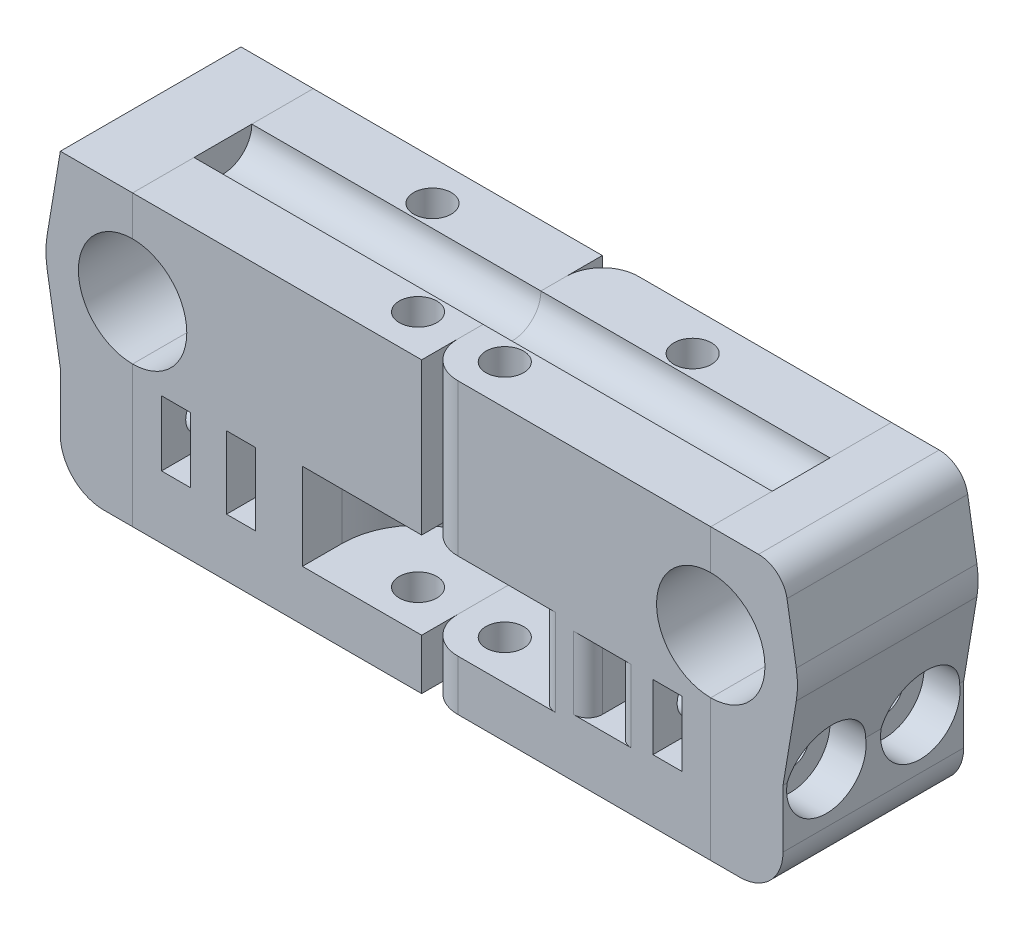
SolidWorks part; units mm, degrees
ref_plane "Front Plane" through (0, 0, 0) normal (0, 0, 1) x (1, 0, 0)
ref_plane "Top Plane" through (0, 0, 0) normal (0, 1, 0) x (1, 0, 0)
ref_plane "Right Plane" through (0, 0, 0) normal (1, 0, 0) x (0, 0, -1)
sketch "Sketch1" plane through (0, 0, 0) normal (0, 0, 1) x (1, 0, 0)
  line L0 (-15, 7) -> (-15, 0) construction
  line L1 (25, -20) -> (-25, -20)
  line L2 (25, -20) -> (25, 20)
  line L3 (25, 20) -> (-25, 20)
  line L4 (-25, -20) -> (-25, 20)
  line L5 (25, -20) -> (-25, 20) construction
  line L6 (25, 20) -> (-25, -20) construction
  line L7 (-15, 0) -> (0, 0) construction
  line L8 (-15, 7) -> (-15, -8) construction
  line L9 (-15, -8) -> (12.294, -8) construction
  line L10 (12.294, -8) -> (12.294, 8) construction
  line L11 (0, 0) -> (12.294, 0) construction
  circle A2 centre (-15, 7) radius 7.5
  point P0 (0, 0)
  dimension "D2" = 10
  dimension "D3" = 50
  dimension "D5" = 15
  dimension "D4" = 40
  dimension "D6" = 16
extrude "Boss-Extrude1" add sketch "Sketch1" along normal blind 25 contours A2 L3 L4 L1 L2
sketch "Sketch2" plane through (25, 0, 0) normal (1, 0, 0) x (0, 0, -1)
  line L0 (-25, 20) -> (0, -20) construction
  line L1 (-12.5, 20) -> (-12.5, -20) construction
  line L2 (-25, 20) -> (0, 20) construction
  circle A0 centre (-12.5, 20) radius 4
  circle A1 centre (-12.5, -20) radius 4
  point P7 (-12.5, 0)
  dimension "D2" = 8
extrude "Cut-Extrude1" cut sketch "Sketch2" against normal offset from surface (40 mm away) 10 up to face at (-25, 0, 12.5)
sketch "Sketch4" plane through (0, 20, 0) normal (0, 1, 0) x (1, 0, 0)
  line L0 (-15, -12.5) -> (13, -12.5) construction
  line L1 (19, -19.5) -> (7, -19.5) construction
  line L2 (19, -19.5) -> (19, -5.5) construction
  line L3 (19, -5.5) -> (7, -5.5) construction
  line L4 (7, -19.5) -> (7, -5.5) construction
  line L5 (19, -19.5) -> (7, -5.5) construction
  line L6 (19, -5.5) -> (7, -19.5) construction
  line L7 (-15, -8.5) -> (-15, -16.5) construction
  line L9 (-5.4237, 0) -> (-5.4237, -25)
  line L17 (-25, -25) -> (-25, 0) construction
  circle A0 centre (19, -19.5) radius 2.6
  circle A1 centre (7, -5.5) radius 2.6
  point P0 (13, -12.5)
  dimension "D3" = 5.2
  dimension "D1" = 12
  dimension "D2" = 14
  dimension "D4" = 32
extrude "Cut-Extrude2" cut sketch "Sketch4" against normal through all contours A1 | A0
sketch "Sketch7" plane through (0, 20, 0) normal (0, 1, 0) x (1, 0, 0)
  line L0 (9, 14) -> (9, -25)
  line L2 (21, -39) -> (21, 0)
  point P6 (9, -5.5)
  point P12 (21, -19.5)
sketch "Sketch16" plane through (0, 0, 0) normal (0, 0, -1) x (-1, 0, 0)
  line L1 (25, -20) -> (25, 20) construction
  line L2 (25, 20) -> (26.8369, 8.9716)
  line L3 (25, -6) -> (26.8369, 5.0284)
  line L4 (25, 20) -> (25, -6)
  circle A0 centre (15, 7) radius 12
  point P5 (27, 7)
  line M11 (25, -20) -> (25, 20)
  dimension "D1" = 2
extrude "Boss-Extrude2" add sketch "Sketch16" against normal up to surface (25 mm away) contours A0 L3 M11 | A0 L4 | A0 L2 M11
sketch "Sketch6" plane through (0, 0, 25) normal (0, 0, 1) x (1, 0, 0)
  line L0 (9.6, 20) -> (4.4, 20) construction
  line L1 (-2, -2) -> (2, -2)
  line L2 (-2, -2) -> (-2, -12)
  line L3 (-2, -12) -> (2, -12)
  line L4 (2, -2) -> (2, -12)
  line L5 (-2, -2) -> (2, -12) construction
  line L6 (-2, -12) -> (2, -2) construction
  point P0 (0, -7)
  point P5 (0, 0)
  point P6 (9, 20)
  dimension "D1" = 2
  dimension "D2" = 4
  dimension "D3" = 10
  dimension "D4" = 7
extrude "Cut-Extrude3" cut sketch "Sketch6" against normal through all
sketch "Sketch8" plane through (0, 20, 0) normal (0, 1, 0) x (1, 0, 0)
  line L0 (19, -9) -> (29.5, -9)
  line L1 (29.5, -9) -> (29.5, -30)
  line L2 (29.5, -30) -> (19, -30)
  line L3 (8.5, -19.5) -> (8.5, -30)
  line L4 (8.5, -30) -> (19, -30)
  arc A0 (19, -9) -> (8.5, -19.5) centre (19, -19.5) ccw
  dimension "D1" = 21
extrude "Cut-Extrude4" cut sketch "Sketch8" against normal blind 12 from offset 21 offset against normal yes
sketch "Sketch11" plane through (0, 20, 0) normal (0, 1, 0) x (1, 0, 0)
  line L1 (16, -5) -> (16, -10)
  line L2 (7, -16) -> (26.2266, -16)
  line L4 (16, -10) -> (26.2266, -10)
  line L5 (26.2266, -16) -> (26.2266, -10)
  line L7 (-3.5, -5.5) -> (-3.5, 3.5)
  line L8 (-3.5, 3.5) -> (16, 3.5)
  line L9 (16, -5) -> (16, 3.5)
  arc A0 (-3.5, -5.5) -> (7, -16) centre (7, -5.5) ccw
  dimension "D1" = 21
  dimension "D2" = 6
extrude "Cut-Extrude5" cut sketch "Sketch11" against normal blind 12 from offset 8 offset against normal yes
sketch "Sketch12" plane through (-25, 0, 0) normal (-1, 0, 0) x (0, 0, 1)
  line L0 (0, -20) -> (0, -6) construction
  line L1 (25, -20) -> (25, -6) construction
  line L2 (6, -6.8649) -> (19, -6.8649)
  circle A0 centre (19, -6.8649) radius 2.65
  circle A1 centre (6, -6.8649) radius 2.65
  dimension "D3" = 5.3
  dimension "D1" = 6
  dimension "D2" = 6
extrude "Cut-Extrude6" cut sketch "Sketch12" against normal blind 22
sketch "Sketch13" plane through (-25, 0, 0) normal (-1, 0, 0) x (0, 0, 1)
  line L2 (3.6139, -11.3715) -> (8.6019, -11.3715)
  line L3 (8.6019, -11.3715) -> (11.2038, -6.8649)
  line L4 (11.2038, -6.8649) -> (8.6019, -2.3583)
  line L5 (8.6019, -2.3583) -> (6, -2.3583)
  line L8 (21.5979, -2.3031) -> (16.2977, -2.4268)
  line L9 (16.2977, -2.4268) -> (13.8053, -6.9861)
  line L10 (13.8053, -6.9861) -> (16.5076, -11.4243)
  line L11 (16.5076, -11.4243) -> (21.1364, -11.3163)
  line L13 (6, -2.3583) -> (-2.7714, -2.3583)
  line L15 (3.6139, -11.3715) -> (-2.7714, -11.3715)
  line L16 (-2.7714, -2.3583) -> (-2.7714, -11.3715)
  line L17 (21.5979, -2.3031) -> (27.8928, -2.3031)
  line L19 (21.1364, -11.3163) -> (27.8928, -11.3163)
  line L20 (27.8928, -2.3031) -> (27.8928, -11.3163)
  line L21 (23.6085, -5.7809) -> (22.3774, -3.7591) [skipped]
  line L22 (22.243, -10.314) -> (23.3785, -8.237) [skipped]
  line L23 (2.0972, -4.6116) -> (0.9136, -6.6616) [skipped]
  line L24 (2.0972, -9.1182) -> (3.2807, -11.1682) [skipped]
  arc A0 (5.981, -11.3715) -> (6.019, -2.3583) centre (6, -6.8649) ccw construction
  arc A1 (19.1195, -2.3609) -> (18.8805, -11.369) centre (19, -6.8649) ccw construction
  dimension "D1" = 9
extrude "Cut-Extrude7" cut sketch "Sketch13" against normal blind 4 from offset 14 offset against normal yes
sketch "Sketch14" plane through (-25, 0, 0) normal (-1, 0, 0) x (0, 0, 1)
  circle A0 centre (6, -6.8649) radius 5.5
  circle A1 centre (19, -6.8649) radius 5.5
  dimension "D1" = 11
extrude "Cut-Extrude8" cut sketch "Sketch14" against normal blind 5 and the other way blind 10
sketch "Sketch15" plane through (0, 0, 0) normal (0, 0, -1) x (-1, 0, 0)
  line L0 (15, 7) -> (15, -0.5) construction
  circle A0 centre (15, 7) radius 7.5 construction
ref_plane "Plane1" through (-15, 0, 0) normal (-1, 0, 0) x (0, 0, 1)
sketch "Sketch19" plane through (0, 0, 0) normal (0, 0, -1) x (-1, 0, 0)
  line L0 (15, 7) -> (15, -20.7299) construction
  line L1 (11, -6.8649) -> (15, -6.8649) construction
  line L2 (11, -2.3583) -> (11, -11.3715) construction
  line L3 (25, -7.7299) -> (26.8369, -18.7583)
  line L4 (25, -20) -> (25, -6) construction
  line L5 (25, -6) -> (26.8369, 5.0284) construction
  line L6 (15, -32.7299) -> (3, -32.7299)
  line L7 (3, -32.7299) -> (0, -20)
  line L8 (-25, -20) -> (25, -20) construction
  circle A0 centre (15, -20.7299) radius 7.5
  circle A1 centre (15, 7) radius 7.5 construction
  circle A2 centre (15, -20.7299) radius 12
  arc A3 (26.8369, 5.0284) -> (26.8369, 8.9716) centre (15, 7) ccw construction
sketch "Sketch22" plane through (-20, 0, 0) normal (-1, 0, 0) x (0, 0, 1)
  circle A0 centre (6, -6.8649) radius 5.5
  circle A1 centre (19, -6.8649) radius 5.5
split "Split1" trim tools "Plane1" bodies to split 109 119 resulting bodies 110 111
fillet "Fillet6" radius 6 1 edges at (-25, -20, 12.5)
mirror "Mirror1" about plane through (25, 0, 25) normal (-1, 0, 0) of bodies 111 110
fillet "Fillet1" radius 5 3 edges at (25, 0, 0) (25, -16.5, 25) (25, 9.5, 25)
fillet "Fillet2" radius 2 9 edges at (48, -7, 0) (52, -7, 0) (53.5, 6, 0) (34, 6, 0) (25, 6, 10) (25, 6, 16) (48, -7, 25) (52, -7, 25) (41.5, -7, 25)
fillet "Fillet3" radius 4 1 edges at (75, 20, 12.5)
fillet "Fillet4" radius 5 1 edges at (25, -7, 9)
